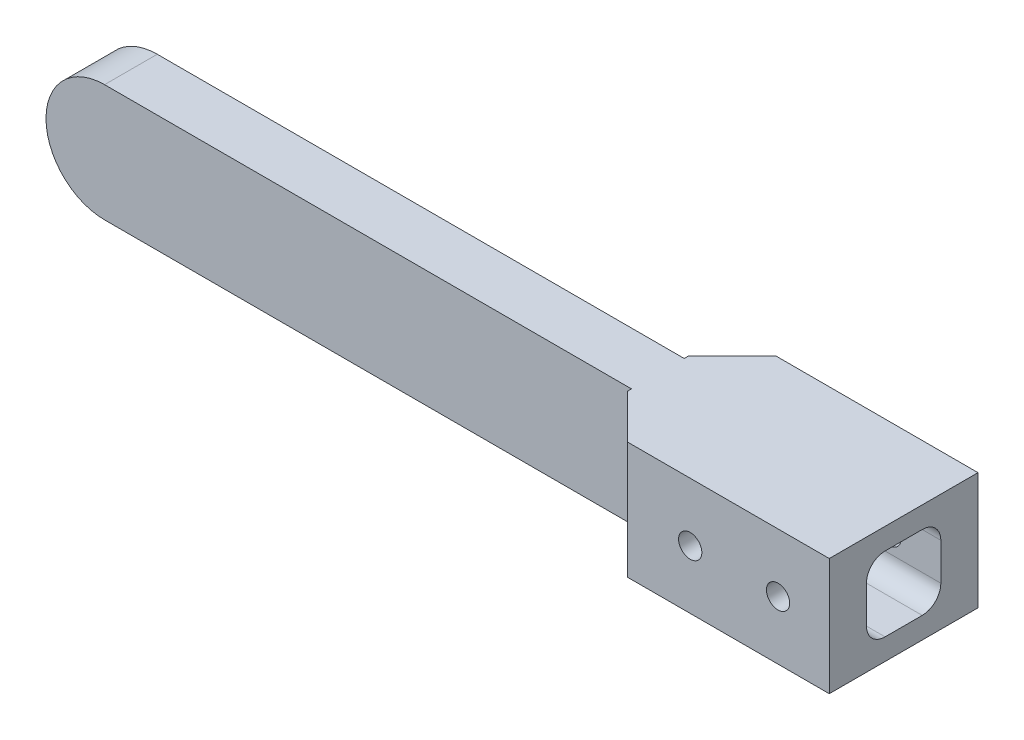
SolidWorks part; units mm, degrees
ref_plane "Alzado" through (0, 0, 0) normal (0, 0, 1) x (1, 0, 0)
ref_plane "Planta" through (0, 0, 0) normal (0, 1, 0) x (1, 0, 0)
ref_plane "Vista lateral" through (0, 0, 0) normal (1, 0, 0) x (0, 0, -1)
sketch "Croquis1" plane through (0, 0, 0) normal (0, 1, 0) x (1, 0, 0)
  line L0 (283.9431, 16.4) -> (283.9431, -34.4)
  line L1 (283.9431, -34.4) -> (215, -34.4)
  line L2 (215, -34.4) -> (200, -19.4)
  line L3 (200, -19.4) -> (200, -18)
  line L4 (200, -18) -> (0, -18)
  line L5 (0, -18) -> (0, 0)
  line L6 (0, 0) -> (200, 0)
  line L7 (200, 0) -> (200, 1.4)
  line L8 (200, 1.4) -> (215, 16.4)
  line L9 (215, 16.4) -> (283.9431, 16.4)
  point P10 (0, -9)
  point P11 (283.9431, -9)
  dimension "D1" = 200
  dimension "D2" = 283.9431
  dimension "D3" = 50.8
  dimension "D4" = 18
  dimension "D5" = 1.4
  dimension "D6" = 1.4
extrude "Saliente-Extruir1" add sketch "Croquis1" along normal blind 40
fillet "Redondeo1" 2 edges at (0, 40, 9) (0, 0, 9) type full round first side face at (179.7886, 40, 9) second side face at (179.7886, 0, 9) middle face at (0, 20, 9)
sketch "Croquis2" plane through (0, 0, 18) normal (0, 0, 1) x (1, 0, 0)
  line L0 (200, 40) -> (200, 0) construction
  line L1 (200, 26) -> (20, 26)
  line L2 (200, 26) -> (200, 14)
  line L3 (200, 14) -> (20, 14)
  line L4 (20, 26) -> (20, 14)
  line L5 (215, 40) -> (215, 0) construction
  point P6 (200, 20)
  point P9 (215, 20)
  point P11 (20, 20)
  dimension "D1" = 12
sketch "Croquis3" plane through (283.9431, 0, 0) normal (1, 0, 0) x (0, 0, -1)
  line L0 (-34.4, 0) -> (16.4, 0) construction
  line L1 (-21.7, 32.7) -> (3.7, 32.7)
  line L2 (-21.7, 32.7) -> (-21.7, 7.3)
  line L3 (-21.7, 7.3) -> (3.7, 7.3)
  line L4 (3.7, 32.7) -> (3.7, 7.3)
  line L5 (16.4, 40) -> (16.4, 0) construction
  point P4 (-9, 7.3)
  point P7 (-9, 0)
  point P8 (3.7, 20)
  point P11 (16.4, 20)
  dimension "D1" = 25.4
  dimension "D2" = 25.4
extrude "Cortar-Extruir2" cut sketch "Croquis3" against normal blind 65
sketch "Croquis4" plane through (0, 0, 34.4) normal (0, 0, 1) x (1, 0, 0)
  line L0 (236.4431, 20) -> (266.4431, 20) construction
  line L1 (283.9431, 40) -> (283.9431, 0) construction
  circle A0 centre (266.4431, 20) radius 3.9688
  circle A1 centre (236.4431, 20) radius 3.9687
  point P6 (283.9431, 20)
  dimension "D1" = 7.9375
  dimension "D2" = 30
  dimension "D3" = 17.5
extrude "Cortar-Extruir3" cut sketch "Croquis4" against normal through all
fillet "Redondeo3" radius 6.35 4 edges at (251.4431, 32.7, -3.7) (251.4431, 32.7, 21.7) (251.4431, 7.3, 21.7) (251.4431, 7.3, -3.7)
